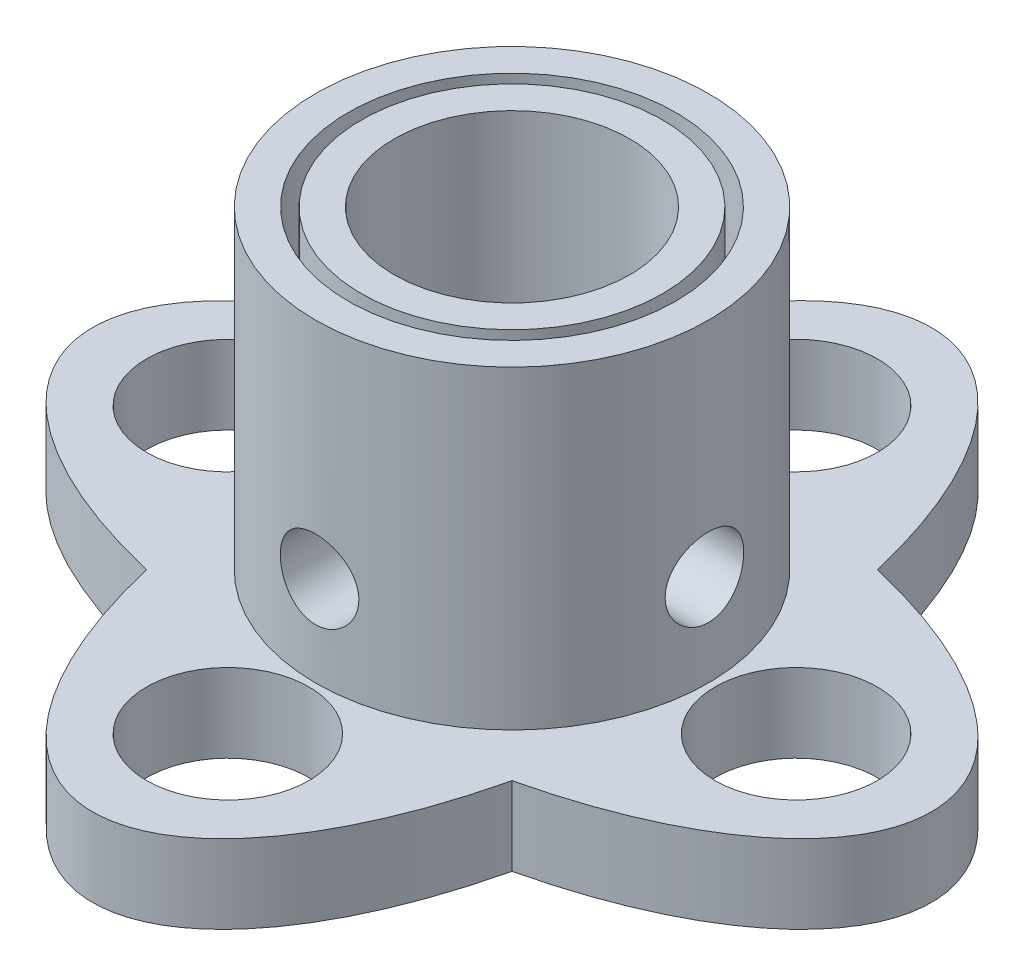
SolidWorks part; units mm, degrees
ref_plane "Front Plane" through (0, 0, 0) normal (0, 0, 1) x (1, 0, 0)
ref_plane "Top Plane" through (0, 0, 0) normal (0, 1, 0) x (1, 0, 0)
ref_plane "Right Plane" through (0, 0, 0) normal (1, 0, 0) x (0, 0, -1)
sketch "Sketch1" plane through (0, 0, 0) normal (0, 1, 0) x (1, 0, 0)
  line L0 (0, 0) -> (-12.8865, 0) construction
  circle A0 centre (0, 0) radius 4.5
  circle A2 centre (-10.8515, 0) radius 3.1
  circle A3 centre (0, 10.8515) radius 3.1
  circle A4 centre (10.8515, 0) radius 3.1
  circle A5 centre (0, -10.8515) radius 3.1
  circle A6 centre (10.8515, 0) radius 3.1
  circle A7 centre (-10.8515, 0) radius 3.1
  circle A8 centre (10.8515, 0) radius 3.1
  circle A9 centre (0, 0) radius 7.5
  ellipse E0 centre (0, 0) end of major axis (-16.0181, 0) minor radius 7.75 (-6.9764, 6.9764) -> (-6.9764, -6.9764) ccw
  ellipse E1 centre (0, 0) end of major axis (0, -16.0181) minor radius 7.75 (-6.9764, -6.9764) -> (6.9764, -6.9764) ccw
  ellipse E2 centre (0, 0) end of major axis (16.0181, 0) minor radius 7.75 (-6.9764, 6.9764) -> (-6.9764, -6.9764) ccw
  ellipse E3 centre (0, 0) end of major axis (0, 16.0181) minor radius 7.75 (-6.9764, -6.9764) -> (6.9764, -6.9764) ccw
  ellipse E4 centre (0, 0) end of major axis (-16.0181, 0) minor radius 7.75 (-6.9764, 6.9764) -> (-6.9764, -6.9764) ccw
  ellipse E5 centre (0, 0) end of major axis (16.0181, 0) minor radius 7.75 (-6.9764, 6.9764) -> (-6.9764, -6.9764) ccw
  ellipse E6 centre (0, 0) end of major axis (16.0181, 0) minor radius 7.75 (-6.9764, 6.9764) -> (-6.9764, -6.9764) ccw
  ellipse E7 centre (0, 0) end of major axis (0, -16.0181) minor radius 7.75 (6.9764, 6.9764) -> (-6.9764, 6.9764) ccw
  ellipse E8 centre (0, 0) end of major axis (0, 16.0181) minor radius 7.75 (6.9764, 6.9764) -> (-6.9764, 6.9764) ccw
  ellipse E9 centre (0, 0) end of major axis (-16.0181, 0) minor radius 7.75 (6.9764, -6.9764) -> (6.9764, 6.9764) ccw
  ellipse E10 centre (0, 0) end of major axis (-16.0181, 0) minor radius 7.75 (6.9764, -6.9764) -> (6.9764, 6.9764) ccw
  ellipse E11 centre (0, 0) end of major axis (16.0181, 0) minor radius 7.75 (6.9764, -6.9764) -> (6.9764, 6.9764) ccw
  ellipse E12 centre (0, 0) end of major axis (16.0181, 0) minor radius 7.75 (6.9764, -6.9764) -> (6.9764, 6.9764) ccw
  ellipse E13 centre (0, 0) end of major axis (16.0181, 0) minor radius 7.75 (6.9764, -6.9764) -> (6.9764, 6.9764) ccw
  point P37 (0, 0)
  point P59 (0, 0)
  dimension "D1" = 6.2
  dimension "D2" = 4
  dimension "D4" = 9
  dimension "D5" = 3
  dimension "D3" = 4
extrude "Boss-Extrude1" add sketch "Sketch1" along normal blind 3 contours E1 E9 E7 E0 A3 A4 A5 A9 A2 region at (0.0207, 0, -15.565)
extrude "Boss-Extrude2" add sketch "Sketch1<3>" along normal blind 10 contours A0 A9 region at (-7.2879, 0, 0)
sketch "Sketch1<3>" plane through (0, 0, 0) normal (0, 1, 0) x (1, 0, 0) same geometry as "Sketch1"
sketch "Sketch2" plane through (0, 0, 0) normal (0, 0, 1) x (1, 0, 0)
  line L0 (0, 10) -> (0, 3) construction
  line L1 (7.5, 10) -> (-7.5, 10) construction
  line L2 (6.9764, 3) -> (-6.9764, 3) construction
  line L3 (0, 3) -> (0, 6.4326) construction
  line L4 (0, 6.4326) -> (7.5, 6.5) construction
  line L5 (7.5, 3) -> (7.5, 10) construction
  circle A0 centre (0, 6.4326) radius 1.5
extrude "Cut-Extrude1" cut sketch "Sketch2" against normal through all both and the other way through all
sketch "Sketch3" plane through (0, 0, 0) normal (1, 0, 0) x (0, 0, -1)
  line L0 (0, 10) -> (0, 3) construction
  line L1 (4.5, 10) -> (-4.5, 10) construction
  line L2 (6.9764, 3) -> (-6.9764, 3) construction
  line L3 (0, 3) -> (0, 6.5) construction
  line L4 (0, 6.5) -> (7.3488, 6.5) construction
  circle A0 centre (0, 6.5) radius 1.5
  spline S0 degree 2 poles (7.5, 4.9326) (7.2, 6.4326) (7.5, 7.9326) knots 0 0 0 1 1 1 weights 0.006 0.0075 0.009 construction
extrude "Cut-Extrude2" cut sketch "Sketch3" against normal through all both and the other way through all
sketch "Sketch29" plane through (0, 10, 0) normal (0, 1, 0) x (1, 0, 0)
  circle A0 centre (0, 0) radius 7.5
  circle A1 centre (0, 0) radius 4.5
extrude "Boss-Extrude3" add sketch "Sketch29" along normal blind 5
sketch "Sketch30" plane through (0, 15, 0) normal (0, 1, 0) x (1, 0, 0)
  line L0 (0, 0) -> (-4.5, 0) construction
  line L1 (-4.5, 0) -> (-7.5, 0) construction
  line L2 (-7.5, 0) -> (-6, 0) construction
  line L3 (-6, 0) -> (-6, -1.4178) construction
  circle A0 centre (0, 0) radius 4.5 construction
  circle A1 centre (0, 0) radius 7.5 construction
  circle A2 centre (0, 0) radius 7.5 construction
  circle A3 centre (0, 0) radius 6
extrude "Cut-Extrude-Thin1" cut sketch "Sketch30" against normal blind 5 thin contours A3 thin type mid plane wall 0.5
